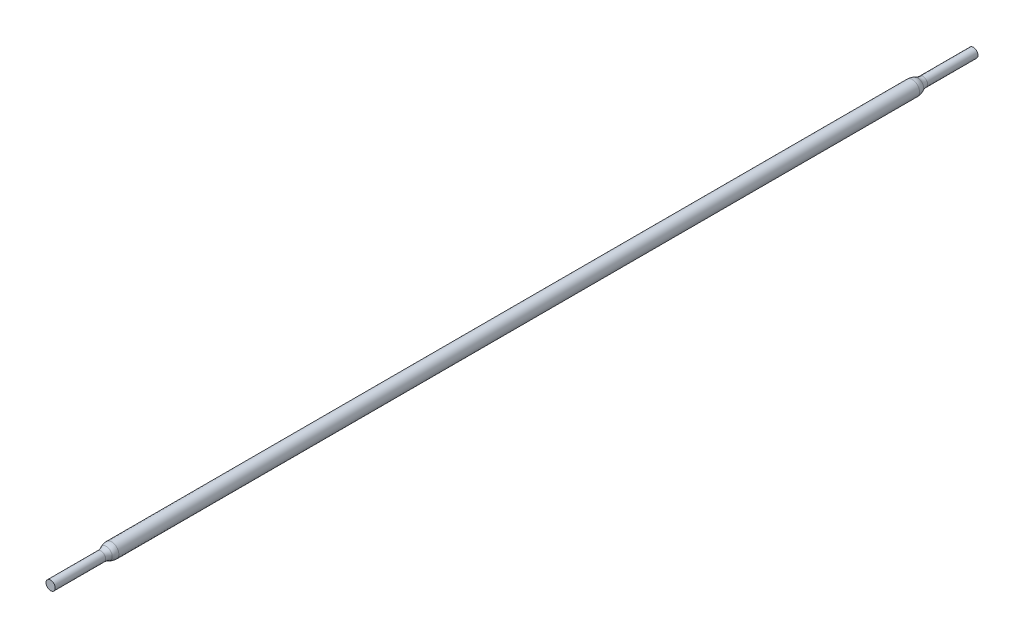
SolidWorks part; units mm, degrees
ref_plane "Front Plane" through (0, 0, 0) normal (0, 0, 1) x (1, 0, 0)
ref_plane "Top Plane" through (0, 0, 0) normal (0, 1, 0) x (1, 0, 0)
ref_plane "Right Plane" through (0, 0, 0) normal (1, 0, 0) x (0, 0, -1)
sketch "Sketch1" plane through (0, 0, 0) normal (0, 0, 1) x (1, 0, 0)
  circle A0 centre (0, 0) radius 4
  dimension "D1" = 8
extrude "Boss-Extrude1" add sketch "Sketch1" along normal blind 50
sketch "Sketch2" plane through (0, 0, 50) normal (0, 0, 1) x (1, 0, 0)
  circle A0 centre (0, 0) radius 6.25
  dimension "D1" = 12.5
extrude "Boss-Extrude2" add sketch "Sketch2" along normal blind 700
sketch "Sketch3" plane through (0, 0, 750) normal (0, 0, 1) x (1, 0, 0)
  circle A0 centre (0, 0) radius 4
  dimension "D1" = 8
extrude "Boss-Extrude3" add sketch "Sketch3" along normal blind 50
fillet "Fillet1" radius 10 2 edges at (4, 0, 50) (4, 0, 750)
fillet "Fillet2" radius 10 2 edges at (6.25, 0, 750) (6.25, 0, 50)
